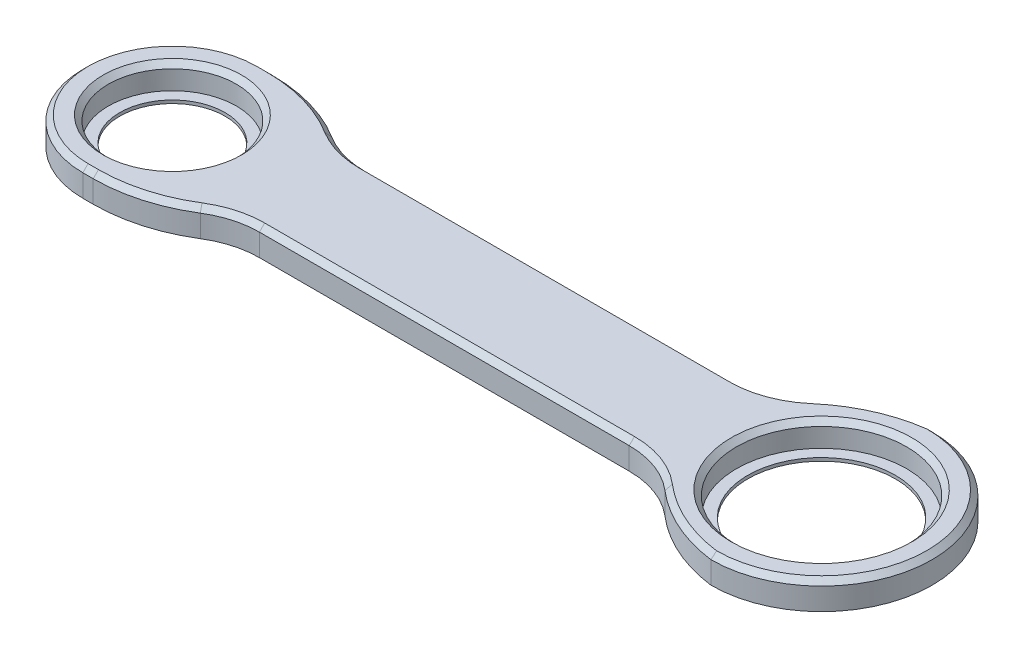
SolidWorks part; units mm, degrees
ref_plane "Front Plane" through (0, 0, 0) normal (0, 0, 1) x (1, 0, 0)
ref_plane "Top Plane" through (0, 0, 0) normal (0, 1, 0) x (1, 0, 0)
ref_plane "Right Plane" through (0, 0, 0) normal (1, 0, 0) x (0, 0, -1)
sketch "Sketch1" plane through (0, 0, 0) normal (0, 1, 0) x (1, 0, 0)
  line L0 (61.625, 0) -> (-61.625, 0) construction
  line L1 (61.625, -21) -> (-61.625, -21)
  line L2 (61.625, 21) -> (-61.625, 21)
  line L3 (-35.1066, 26.5458) -> (35.1066, 26.5458) construction
  line L4 (-35.1066, 43.0915) -> (35.1066, 43.0915)
  line L5 (-35.1066, 10) -> (35.1066, 10)
  line L6 (-35.1066, -26.5458) -> (35.1066, -26.5458) construction
  line L7 (-35.1066, -10) -> (35.1066, -10)
  line L8 (-35.1066, -43.0915) -> (35.1066, -43.0915)
  arc A0 (61.625, -21) -> (61.625, 21) centre (61.625, 0) ccw
  arc A1 (-61.625, 21) -> (-61.625, -21) centre (-61.625, 0) ccw
  circle A2 centre (-61.625, 0) radius 12.15
  arc A3 (-35.1066, 43.0915) -> (-35.1066, 10) centre (-35.1066, 26.5458) ccw
  arc A4 (35.1066, 10) -> (35.1066, 43.0915) centre (35.1066, 26.5458) ccw
  arc A5 (-35.1066, -10) -> (-35.1066, -43.0915) centre (-35.1066, -26.5458) ccw
  arc A6 (35.1066, -43.0915) -> (35.1066, -10) centre (35.1066, -26.5458) ccw
  circle A7 centre (61.625, 0) radius 16.15
  point P2 (0, 0)
  point P12 (0, 26.5458)
  point P19 (0, -26.5458)
  point P24 (35.1066, -27.5458)
  dimension "D2" = 24.3
  dimension "D3" = 21
  dimension "D6" = 32.3
  dimension "D1" = 123.25
  dimension "D4" = 10
  dimension "D5" = 10
extrude "Boss-Extrude1" add sketch "Sketch1" along normal blind 5.2 contours A6 L1 A0 L2 A4 L5 A3 A1 A5 L7 A7 A2 region at (-6.7765, 0, 0)
sketch "Sketch4" plane through (0, 5.2, 0) normal (0, 1, 0) x (1, 0, 0)
  line L0 (-61.625, 17) -> (-38.9705, 17)
  line L1 (-38.9705, 17) -> (-43.408, 33.3429)
  line L2 (-43.408, 33.3429) -> (-92.9845, 23.091)
  line L3 (-92.9845, 23.091) -> (-92.9845, -9.501)
  line L4 (-92.9845, -9.501) -> (-86.7109, -27.0976)
  line L5 (-86.7109, -27.0976) -> (-50.7369, -31.9731)
  line L6 (-50.7369, -31.9731) -> (-37.8994, -29.5848)
  line L7 (-37.8994, -29.5848) -> (-38.9705, -17)
  line L8 (-38.9705, -17) -> (-61.625, -17)
  arc A0 (-61.625, 17) -> (-61.625, -17) centre (-61.625, 0) ccw
  arc A1 (-35.1066, -10) -> (-35.1066, -43.0915) centre (-35.1066, -26.5458) ccw construction
  dimension "D1" = 17
extrude "Cut-Extrude1" cut sketch "Sketch4" against normal through all
fillet "Fillet1" radius 30 4 edges at (50.6953, 2.6, -21) (50.6953, 2.6, 21) (-48.6211, 2.6, -17) (-48.6211, 2.6, 17)
chamfer "Chamfer1" distance 1 angle 45 16 edges at (61.625, 5.2, 16.15) (-61.625, 5.2, 12.15) (0, 5.2, -10) (-39.6437, 5.2, -10.6342) (40.8569, 5.2, -11.0314) (53.2443, 5.2, -18.6519) (82.625, 5.2, 0) (53.2443, 5.2, 18.6519) (-39.6437, 5.2, 10.6342) (40.8569, 5.2, 11.0314) (0, 5.2, 10) (-51.4288, 5.2, -15.85) (-60.6402, 5.2, -17) (-78.625, 5.2, 0) (-60.6402, 5.2, 17) (-51.4288, 5.2, 15.85)
sketch "Sketch2" plane through (0, 0, 0) normal (0, -1, 0) x (1, 0, 0)
  circle A0 centre (-61.625, 0) radius 10
  circle A1 centre (-61.625, 0) radius 14.7553
  circle A2 centre (61.625, 0) radius 14
  circle A3 centre (61.625, 0) radius 19.0252
  dimension "D1" = 20
  dimension "D2" = 28
extrude "Boss-Extrude2" add sketch "Sketch2" against normal blind 0.6
sketch "Sketch3" plane through (0, 5.4, 0) normal (0, 1, 0) x (1, 0, 0)
  line L0 (77.77, 28.8659) -> (77.77, -26.5149) construction
  line L1 (0, 0) -> (86.87, 0) construction
  line L2 (77.775, 17.2779) -> (77.775, -15.919) construction
  circle A1 centre (61.625, 0) radius 16.15 construction
  dimension "D1" = 86.87
  dimension "D2" = 9.1
